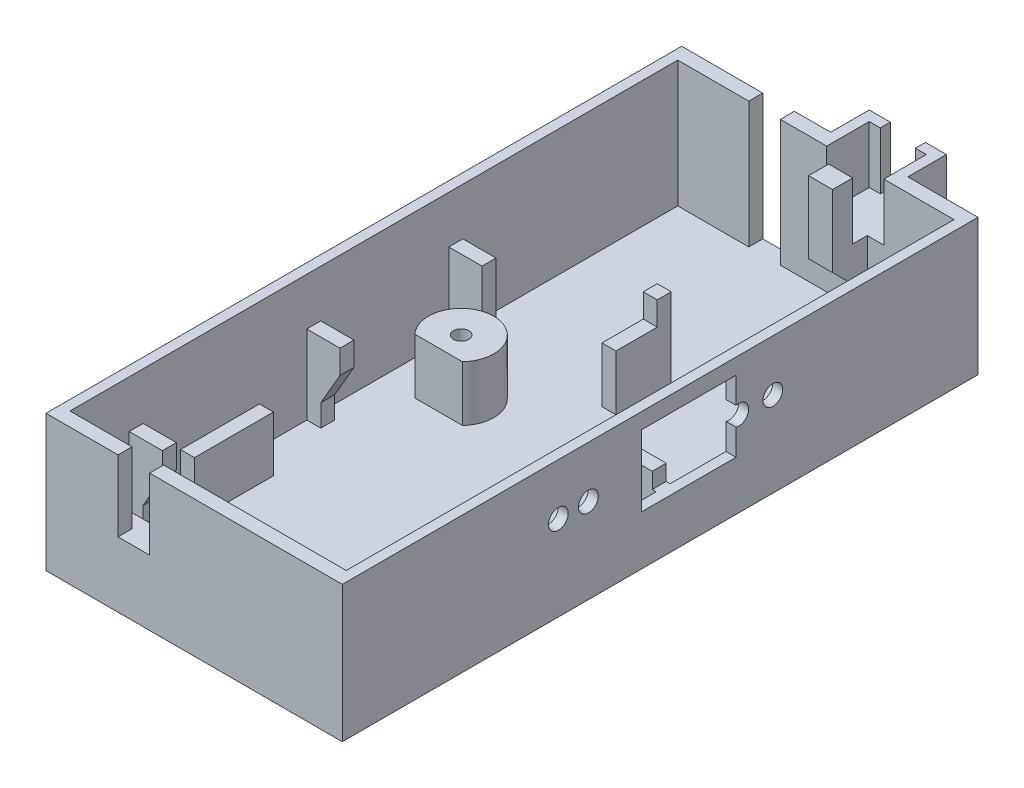
SolidWorks part; units mm, degrees
ref_plane "Front Plane" through (0, 0, 0) normal (0, 0, 1) x (1, 0, 0)
ref_plane "Top Plane" through (0, 0, 0) normal (0, 1, 0) x (1, 0, 0)
ref_plane "Right Plane" through (0, 0, 0) normal (1, 0, 0) x (0, 0, -1)
sketch "Sketch2" plane through (0, 0, 0) normal (0, 0, 1) x (1, 0, 0)
  line L0 (-30.2154, 3.088) -> (-30.2154, -12.912)
  line L1 (-30.2154, -12.912) -> (4.7846, -12.912)
  line L2 (4.7846, -12.912) -> (4.7846, 3.088)
  line L3 (-31.4854, 3.088) -> (-31.4854, -14.182)
  line L4 (-31.4854, -14.182) -> (6.0546, -14.182)
  line L5 (6.0546, -14.182) -> (6.0546, 3.088)
  line L6 (-31.4854, 3.088) -> (-30.2154, 3.088)
  line L7 (4.7846, 3.088) -> (6.0546, 3.088)
  dimension "D1" = 16
  dimension "D2" = 16
  dimension "D3" = 35
  dimension "D4" = 1.27
extrude "Boss-Extrude1" add sketch "Sketch2" along normal blind 77
sketch "Sketch3" plane through (0, 0, 77) normal (0, 0, 1) x (1, 0, 0)
  line L1 (-31.4854, 3.088) -> (6.0546, 3.088)
  line L2 (-31.4854, 3.088) -> (-31.4854, -14.182)
  line L3 (-31.4854, -14.182) -> (6.0546, -14.182)
  line L4 (6.0546, 3.088) -> (6.0546, -14.182)
extrude "Boss-Extrude2" add sketch "Sketch3" along normal blind 1.77
sketch "Sketch4" plane through (0, 0, 0) normal (0, 0, -1) x (-1, 0, 0)
  line L1 (-6.0546, 3.088) -> (31.4854, 3.088)
  line L2 (-6.0546, 3.088) -> (-6.0546, -14.182)
  line L3 (-6.0546, -14.182) -> (31.4854, -14.182)
  line L4 (31.4854, 3.088) -> (31.4854, -14.182)
extrude "Boss-Extrude3" add sketch "Sketch4" along normal blind 1.77
sketch "Sketch5" plane through (0, 0, -1.77) normal (0, 0, -1) x (-1, 0, 0)
  line L0 (31.4854, 3.088) -> (-6.0546, 3.088) construction
  line L1 (17.2154, 3.088) -> (21.2154, 3.088)
  line L2 (17.2154, 3.088) -> (17.2154, -12.912)
  line L3 (17.2154, -12.912) -> (21.2154, -12.912)
  line L4 (21.2154, 3.088) -> (21.2154, -12.912)
  line L5 (-4.7846, -12.912) -> (30.2154, -12.912) construction
  line L6 (30.2154, -12.912) -> (30.2154, 3.088) construction
  dimension "D1" = 4
  dimension "D2" = 9
extrude "Cut-Extrude2" cut sketch "Sketch5" against normal blind 1.77
sketch "Sketch6" plane through (0, 3.088, 0) normal (0, 1, 0) x (1, 0, 0)
  line L0 (4.7846, -77) -> (4.7846, 0) construction
  line L1 (-11.3454, 5.39) -> (-4.1054, 5.39)
  line L2 (-11.3454, 5.39) -> (-11.3454, -1.85)
  line L3 (-11.3454, -1.85) -> (-4.1054, -1.85)
  line L4 (-4.1054, 5.39) -> (-4.1054, -1.85)
  line L5 (-12.6154, 6.66) -> (-2.8354, 6.66)
  line L6 (-12.6154, 6.66) -> (-12.6154, -4.39)
  line L7 (-12.6154, -4.39) -> (-2.8354, -4.39)
  line L8 (-2.8354, 6.66) -> (-2.8354, -4.39)
  line L9 (-17.2154, 1.77) -> (6.0546, 1.77) construction
  dimension "D1" = 1.27
  dimension "D2" = 1.27
  dimension "D3" = 8.89
  dimension "D4" = 7.24
  dimension "D5" = 1.27
  dimension "D6" = 2.54
  dimension "D7" = 7.24
  dimension "D8" = 3.62
extrude "button_walls" add sketch "Sketch6" against normal blind 7.24
sketch "Sketch7" plane through (0, -4.152, 0) normal (0, -1, 0) x (1, 0, 0)
  line L1 (-12.6154, 4.39) -> (-2.8354, 4.39)
  line L2 (-12.6154, 4.39) -> (-12.6154, -6.66)
  line L3 (-12.6154, -6.66) -> (-2.8354, -6.66)
  line L4 (-2.8354, 4.39) -> (-2.8354, -6.66)
extrude "button_bottom" add sketch "Sketch7" along normal blind 1.27
sketch "Sketch8" plane through (0, 3.088, 0) normal (0, 1, 0) x (1, 0, 0)
  line L0 (-11.3454, 0) -> (-4.1054, 0) construction
  line L1 (-11.3454, 1.77) -> (-4.1054, 1.77)
  line L2 (-11.3454, 1.77) -> (-11.3454, 0)
  line L3 (-11.3454, 0) -> (-4.1054, 0)
  line L4 (-4.1054, 1.77) -> (-4.1054, 0)
extrude "button_cutout_middle" cut sketch "Sketch8" against normal blind 7.24
sketch "Sketch9" plane through (0, 3.088, 0) normal (0, 1, 0) x (1, 0, 0)
  line L0 (-7.7254, 9.378) -> (-7.7254, -7.9569) construction
  line L1 (-2.8354, 6.66) -> (-12.6154, 6.66) construction
  line L2 (-9.9454, 6.66) -> (-5.4954, 6.66)
  line L3 (-9.9454, 6.66) -> (-9.9454, 5.39)
  line L4 (-9.9454, 5.39) -> (-5.4954, 5.39)
  line L5 (-5.4954, 6.66) -> (-5.4954, 5.39)
  line L6 (-4.1054, 5.39) -> (-11.3454, 5.39) construction
  line L13 (-12.6154, -4.39) -> (-2.8354, -4.39) construction
  line L14 (-12.6154, 0) -> (-9.2454, 0)
  line L15 (-12.6154, 0) -> (-12.6154, -4.39)
  line L16 (-12.6154, -4.39) -> (-9.2454, -4.39)
  line L17 (-9.2454, 0) -> (-9.2454, -4.39)
  line L19 (-2.8354, 0) -> (-6.2054, 0)
  line L20 (-2.8354, 0) -> (-2.8354, -4.39)
  line L21 (-2.8354, -4.39) -> (-6.2054, -4.39)
  line L22 (-6.2054, 0) -> (-6.2054, -4.39)
  dimension "D1" = 4.45
  dimension "D2" = 2.22
  dimension "D3" = 1.52
  dimension "D4" = 1.52
extrude "button_cutout_front_back" cut sketch "Sketch9" against normal blind 7.24
sketch "Sketch10" plane through (0, -4.152, 0) normal (0, 1, 0) x (1, 0, 0)
  line L1 (-12.6154, 0) -> (-9.2454, 0)
  line L2 (-12.6154, 0) -> (-12.6154, -4.39)
  line L3 (-12.6154, -4.39) -> (-9.2454, -4.39)
  line L4 (-9.2454, 0) -> (-9.2454, -4.39)
  line L5 (-2.8354, 0) -> (-6.2054, 0)
  line L6 (-2.8354, 0) -> (-2.8354, -4.39)
  line L7 (-2.8354, -4.39) -> (-6.2054, -4.39)
  line L8 (-6.2054, 0) -> (-6.2054, -4.39)
extrude "button_cutout_bottom" cut sketch "Sketch10" against normal blind 1.27
chamfer "button_Chamfer1" distance 5 angle 45 1 edges at (-7.7254, -5.422, 0)
sketch "Sketch12" plane through (0, -12.912, 0) normal (0, 1, 0) x (1, 0, 0)
  line L0 (4.7846, -77) -> (-30.2154, -77) construction
  line L1 (-30.2154, -77) -> (4.7846, -77)
  line L2 (-30.2154, -77) -> (-30.2154, -75.23)
  line L3 (-30.2154, -75.23) -> (4.7846, -75.23)
  line L4 (4.7846, -77) -> (4.7846, -75.23)
  line L5 (4.7846, -77) -> (4.7846, 0) construction
  line L11 (4.7846, -77) -> (4.7846, 0) construction
  line L12 (-27.9854, -55.23) -> (-26.2154, -55.23)
  line L13 (-27.9854, -55.23) -> (-27.9854, -65.23)
  line L14 (-27.9854, -65.23) -> (-26.2154, -65.23)
  line L15 (-26.2154, -55.23) -> (-26.2154, -65.23)
  line L16 (4.7846, -37.73) -> (-60.4587, -37.73) construction
  line L17 (-2.7154, -35.96) -> (4.7846, -35.96)
  line L18 (-2.7154, -35.96) -> (-2.7154, -37.73)
  line L19 (-2.7154, -37.73) -> (4.7846, -37.73)
  line L20 (4.7846, -35.96) -> (4.7846, -37.73)
  line L21 (-25.7839, -37.73) -> (-19.7648, -37.73)
  line L22 (-54.4351, -21.6) -> (25.4799, -21.6) construction
  line L24 (-12.9854, -19.83) -> (-11.2154, -19.83)
  line L25 (-12.9854, -19.83) -> (-12.9854, -26.83)
  line L26 (-12.9854, -26.83) -> (-11.2154, -26.83)
  line L27 (-11.2154, -19.83) -> (-11.2154, -26.83)
  arc A0 (-19.7648, -37.73) -> (-25.7839, -37.73) centre (-22.7744, -34.8868) ccw
  circle A1 centre (-22.7744, -34.8868) radius 0.9652
  point P29 (-12.1004, -19.83)
  dimension "D11" = 8.2804
  dimension "D12" = 1.9304
  dimension "D1" = 1.77
  dimension "D2" = 31
  dimension "D3" = 1.77
  dimension "D4" = 10
  dimension "D5" = 10
  dimension "D6" = 1.77
  dimension "D7" = 7.5
  dimension "D8" = 37.5
  dimension "D9" = 42.1132
  dimension "D10" = 27.559
  dimension "D13" = 55.4
  dimension "D14" = 1.77
  dimension "D15" = 7
  dimension "D16" = 1.77
  dimension "D17" = 16
extrude "support_pcb_battery" add sketch "Sketch12" along normal blind 7
sketch "Sketch13" plane through (6.0546, 0, 0) normal (1, 0, 0) x (0, 0, -1)
  line L0 (-77, 3.088) -> (-77, -22.3902) construction
  line L1 (-81.5091, -5.912) -> (21.2567, -5.912) construction
  line L3 (-40.8868, 1.088) -> (-28.8868, 1.088)
  line L4 (-40.8868, 1.088) -> (-40.8868, -7.912)
  line L5 (-40.8868, -7.912) -> (-28.8868, -7.912)
  line L6 (-28.8868, 1.088) -> (-28.8868, -7.912)
  circle A0 centre (-51.3968, -3.412) radius 1.25
  circle A1 centre (-47.5868, -3.412) radius 1.25
  circle A2 centre (-24.2188, -3.412) radius 1.25
  point P10 (-28.8868, -3.412)
  point P11 (-34.8868, 1.088)
  dimension "D7" = 2.5
  dimension "D8" = 2.5
  dimension "D11" = 2.5
  dimension "D1" = 12
  dimension "D2" = 2.5
  dimension "D3" = 9
  dimension "D4" = 42.1132
  dimension "D5" = 2.5
  dimension "D6" = 2.5
  dimension "D9" = 25.6032
  dimension "D10" = 29.4132
  dimension "D12" = 2.5
  dimension "D13" = 52.7812
extrude "cutout_usb_3_leds" cut sketch "Sketch13" against normal blind 1.77
sketch "Sketch16" plane through (0, -5.912, 0) normal (0, 1, 0) x (1, 0, 0)
  line L0 (-11.2154, -26.83) -> (-11.2154, -19.83) construction
  line L1 (-12.9854, -19.83) -> (-11.2154, -19.83)
  line L2 (-12.9854, -19.83) -> (-12.9854, -21.6)
  line L3 (-12.9854, -21.6) -> (-11.2154, -21.6)
  line L4 (-11.2154, -19.83) -> (-11.2154, -21.6)
  dimension "D1" = 1.77
extrude "tab_pcb_retainer_len" add sketch "Sketch16" along normal blind 3
sketch "Sketch17" plane through (0, 3.088, 0) normal (0, 1, 0) x (1, 0, 0)
  line L0 (4.7846, -77) -> (-30.2154, -77) construction
  line L1 (-22.3614, -77) -> (-18.3614, -77)
  line L2 (-22.3614, -77) -> (-22.3614, -78.77)
  line L3 (-22.3614, -78.77) -> (-18.3614, -78.77)
  line L4 (-18.3614, -77) -> (-18.3614, -78.77)
  line L5 (6.0546, -78.77) -> (-31.4854, -78.77) construction
  line L7 (4.7846, -77) -> (4.7846, 0) construction
  point P8 (-20.3614, -77)
  dimension "D1" = 25.146
  dimension "D2" = 4
extrude "cutout_back_mot_wires" cut sketch "Sketch17" against normal up to surface (9 mm away) up to face at (-12.7154, -5.912, 76.115)
sketch "Sketch18" plane through (6.0546, 0, 0) normal (1, 0, 0) x (0, 0, -1)
  line L0 (-77, 3.088) -> (-77, -25.415) construction
  line L1 (-78.77, -5.912) -> (19.6061, -5.912) construction
  circle A0 centre (-28.5368, -3.412) radius 1.25
  dimension "D1" = 2.5
  dimension "D2" = 2.5
  dimension "D3" = 48.4632
extrude "cutout_chg_done_led" cut sketch "Sketch18" against normal blind 10
sketch "Sketch19" plane through (0, -12.912, 0) normal (0, 1, 0) x (1, 0, 0)
  line L0 (-30.2154, -77) -> (38.3127, -77) construction
  line L1 (4.7846, 0) -> (4.7846, -88.7648) construction
  line L2 (-26.0154, 10.814) -> (-26.0154, -88.7648) construction
  line L3 (-30.2154, -77) -> (-30.2154, 0) construction
  line L4 (-30.2154, -67.73) -> (-26.0154, -67.73)
  line L5 (-30.2154, -67.73) -> (-30.2154, -69.5)
  line L6 (-30.2154, -69.5) -> (-26.0154, -69.5)
  line L7 (-26.0154, -67.73) -> (-26.0154, -69.5)
  line L9 (-30.2154, -45.23) -> (-26.0154, -45.23)
  line L10 (-30.2154, -45.23) -> (-30.2154, -47)
  line L11 (-30.2154, -47) -> (-26.0154, -47)
  line L12 (-26.0154, -45.23) -> (-26.0154, -47)
  line L13 (-30.2154, -27.23) -> (-26.0154, -27.23)
  line L14 (-30.2154, -27.23) -> (-30.2154, -29)
  line L15 (-30.2154, -29) -> (-26.0154, -29)
  line L16 (-26.0154, -27.23) -> (-26.0154, -29)
  dimension "D1" = 30.8
  dimension "D2" = 1.77
  dimension "D3" = 7.5
  dimension "D4" = 1.77
  dimension "D5" = 30
  dimension "D6" = 1.77
  dimension "D7" = 48
extrude "tab_pcb_retainers_width" add sketch "Sketch19" along normal blind 10
sketch "Sketch20" plane through (0, 0, 69.5) normal (0, 0, 1) x (1, 0, 0)
  line L0 (-26.0154, -2.912) -> (-33.8352, -2.912) construction
  line L1 (-26.0154, -5.912) -> (-34.7157, -5.912) construction
  line L2 (-30.2154, -5.912) -> (-22.3614, -5.912) construction
  line L3 (-26.0154, -2.912) -> (-26.0154, -12.912) construction
  line L4 (-28.4454, -0.8533) -> (-28.4454, -17.345) construction
  line L5 (-30.2154, -5.912) -> (-30.2154, 3.088) construction
  line L9 (-26.0154, -12.912) -> (-26.0154, -5.912)
  line L15 (-26.0154, -5.912) -> (-28.4454, -10.1209)
  line L16 (-28.4454, -10.1209) -> (-28.4454, -12.912)
  line L17 (-28.4454, -12.912) -> (-26.0154, -12.912)
  dimension "D1" = 1.77
  dimension "D2" = 30
extrude "cutout_retainer_tab_1" cut sketch "Sketch20" against normal blind 1.77
sketch "Sketch21" plane through (0, 0, 47) normal (0, 0, 1) x (1, 0, 0)
  line L0 (-26.0154, -5.912) -> (-28.4454, -10.1209)
  line L1 (-28.4454, -10.1209) -> (-28.4454, -12.912)
  line L2 (-28.4454, -12.912) -> (-26.0154, -12.912)
  line L3 (-26.0154, -12.912) -> (-26.0154, -5.912)
extrude "cutout_retainer_tab_2" cut sketch "Sketch21" against normal blind 1.77
